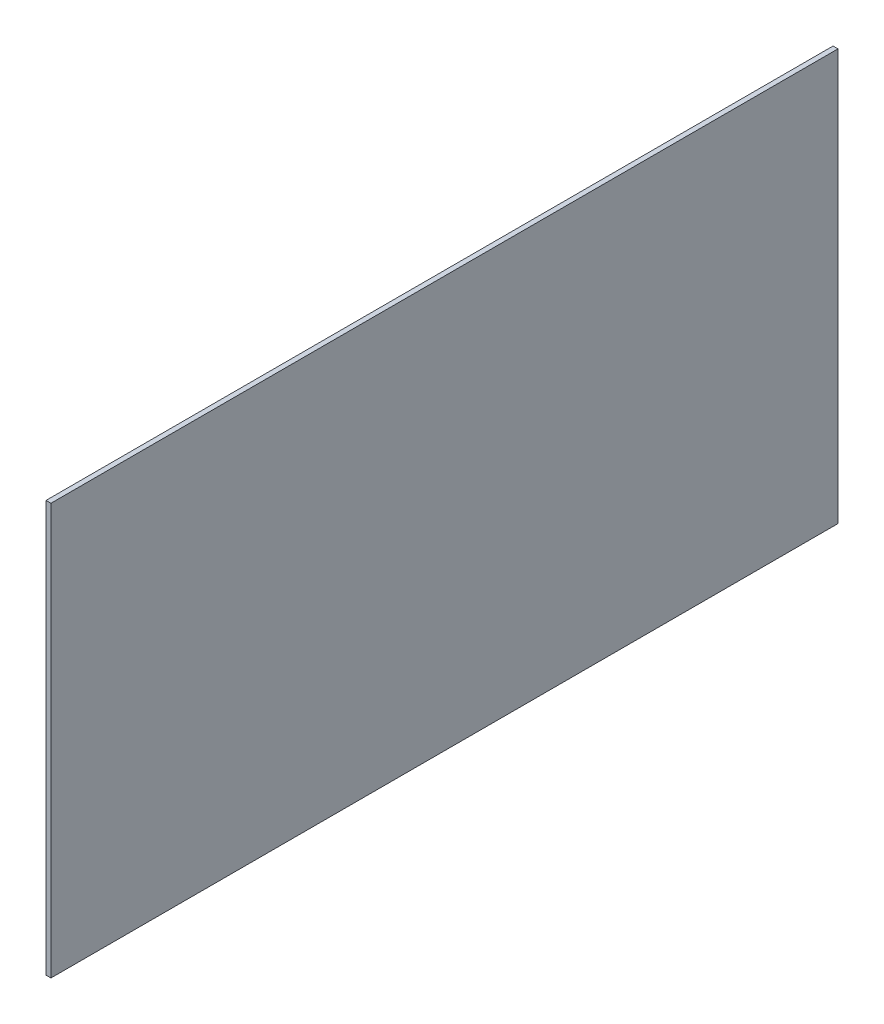
SolidWorks part; units mm, degrees
material "ASTM A36 Steel"
ref_plane "Front Plane" through (0, 0, 0) normal (0, 0, 1) x (1, 0, 0)
ref_plane "Top Plane" through (0, 0, 0) normal (0, 1, 0) x (1, 0, 0)
ref_plane "Right Plane" through (0, 0, 0) normal (1, 0, 0) x (0, 0, -1)
sketch "Sketch1" plane through (0, 0, 0) normal (1, 0, 0) x (0, 0, -1)
  line L0 (0, 0) -> (0, 349.25) construction
  line L1 (0, 0) -> (-596.9, 0) construction
  line L2 (-115.57, 0) -> (-115.57, 222.25)
  line L3 (-115.57, 222.25) -> (-541.02, 222.25)
  line L4 (-541.02, 222.25) -> (-541.02, 0)
  line L5 (-596.9, 0) -> (-115.57, 0)
  dimension "D1" = 349.25
  dimension "D2" = 596.9
  dimension "D3" = 222.25
  dimension "D4" = 115.57
  dimension "D5" = 425.45
extrude "Boss-Extrude1" add sketch "Sketch1" along normal blind 2.667 contours L4 L5 L2 L3 region at (0, 111.125, 328.295)
